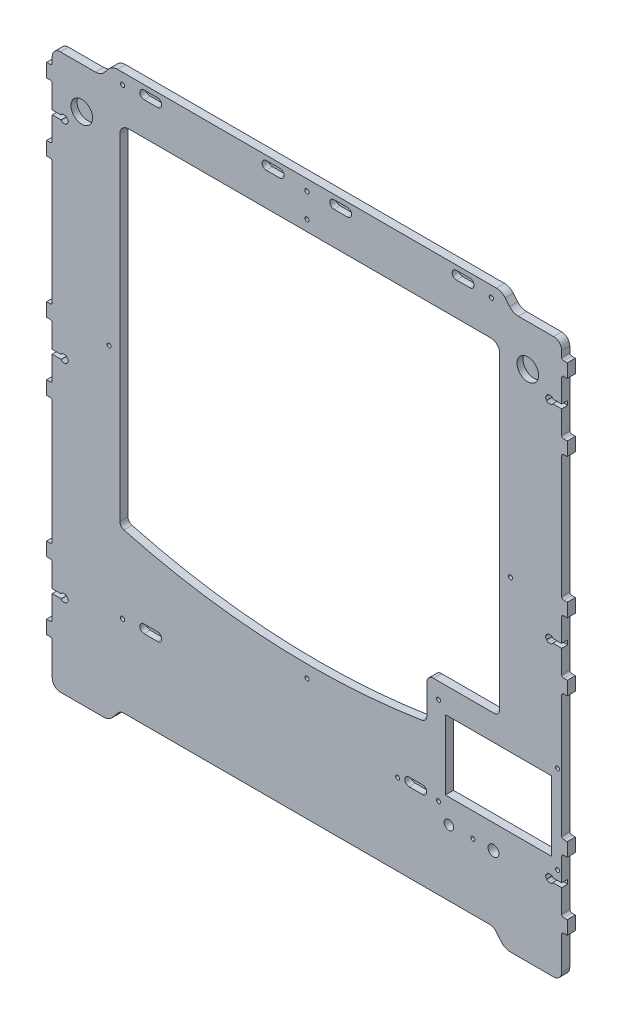
SolidWorks part; units mm, degrees
ref_plane "Alzado" through (0, 0, 0) normal (0, 0, 1) x (1, 0, 0)
ref_plane "Planta" through (0, 0, 0) normal (0, 1, 0) x (1, 0, 0)
ref_plane "Vista lateral" through (0, 0, 0) normal (1, 0, 0) x (0, 0, -1)
sketch "Croquis1" plane through (0, 0, 0) normal (0, 0, 1) x (1, 0, 0)
  line L0 (101.3953, 205.0104) -> (-166.4547, 205.0104)
  line L1 (-34.6047, 239.0104) -> (-34.6047, -170.9896) construction
  line L2 (-172.9547, 198.5104) -> (-172.9547, -49.66)
  line L3 (-222.9547, 187.3104) -> (-34.6047, 187.3104) construction
  line L4 (-128.7797, 34.0104) -> (-128.7797, 187.3104) construction
  line L5 (-222.9547, 205.7604) -> (-222.9547, 168.8604)
  line L6 (107.8953, -30.1228) -> (107.8953, 198.5104)
  line L7 (-222.9547, -87.7396) -> (-222.9547, 2.4604)
  line L8 (153.7453, -87.7396) -> (153.7453, 2.4604)
  line L9 (-227.1047, 167.3104) -> (-224.5047, 167.3104)
  line L10 (103.8762, -34.1419) -> (58.9808, -34.1419)
  line L11 (54.0552, -39.0675) -> (54.0552, -60.8574)
  line L12 (-227.1047, 157.3104) -> (-227.1047, 167.3104)
  line L13 (-224.5047, 157.3104) -> (-227.1047, 157.3104)
  line L14 (-224.5047, -89.2896) -> (-227.1047, -89.2896)
  line L15 (-227.1047, -89.2896) -> (-227.1047, -99.2896)
  line L16 (-34.6047, 34.0104) -> (-222.9547, 34.0104) construction
  line L17 (-227.1047, -99.2896) -> (-224.5047, -99.2896)
  line L21 (-227.1047, -139.2896) -> (-224.5047, -139.2896)
  line L22 (-227.1047, -149.2896) -> (-227.1047, -139.2896)
  line L23 (-224.5047, -149.2896) -> (-227.1047, -149.2896)
  line L25 (-222.9547, -137.7396) -> (-222.9547, -100.8396)
  line L32 (147.7453, -180.9896) -> (115.7453, -180.9896)
  line L36 (100.8221, -170.9896) -> (-170.0314, -170.9896)
  line L37 (-210.4105, 34.0104) -> (-223.8121, 34.0104) construction
  line L38 (-222.9547, 15.5604) -> (-222.9547, 52.4604)
  line L42 (153.7453, 37.4611) -> (153.7453, -87.7396) construction
  line L43 (-227.1047, 14.0104) -> (-224.5047, 14.0104)
  line L44 (-227.1047, 4.0104) -> (-227.1047, 14.0104)
  line L45 (-224.5047, 4.0104) -> (-227.1047, 4.0104)
  line L46 (-224.5047, 64.0104) -> (-227.1047, 64.0104)
  line L47 (-227.1047, 64.0104) -> (-227.1047, 54.0104)
  line L48 (-227.1047, 54.0104) -> (-224.5047, 54.0104)
  line L63 (-34.6047, 34.0104) -> (153.7453, 34.0104) construction
  line L69 (109.234, -177.9533) -> (105.0418, -172.9573)
  line L73 (-222.9547, 155.7604) -> (-222.9547, 65.5604)
  line L74 (-222.9547, 37.4611) -> (-222.9547, -87.7396) construction
  line L75 (-222.9547, -150.8396) -> (-222.9547, -174.9896)
  line L77 (153.7453, -150.8396) -> (153.7453, -174.9896)
  line L81 (157.8953, -99.2896) -> (155.2953, -99.2896)
  line L82 (157.8953, -89.2896) -> (157.8953, -99.2896)
  line L83 (155.2953, -89.2896) -> (157.8953, -89.2896)
  line L84 (155.2953, -149.2896) -> (157.8953, -149.2896)
  line L85 (157.8953, -149.2896) -> (157.8953, -139.2896)
  line L86 (157.8953, -139.2896) -> (155.2953, -139.2896)
  line L87 (153.7453, -137.7396) -> (153.7453, -100.8396)
  line L91 (155.2953, 4.0104) -> (157.8953, 4.0104)
  line L92 (157.8953, 4.0104) -> (157.8953, 14.0104)
  line L93 (157.8953, 14.0104) -> (155.2953, 14.0104)
  line L103 (153.7453, 15.5604) -> (153.7453, 52.4604)
  line L104 (157.8953, 54.0104) -> (155.2953, 54.0104)
  line L105 (157.8953, 64.0104) -> (157.8953, 54.0104)
  line L106 (155.2953, 64.0104) -> (157.8953, 64.0104)
  line L107 (153.7453, 155.7604) -> (153.7453, 65.5604)
  line L108 (155.2953, 157.3104) -> (157.8953, 157.3104)
  line L109 (157.8953, 157.3104) -> (157.8953, 167.3104)
  line L110 (157.8953, 167.3104) -> (155.2953, 167.3104)
  line L115 (153.7453, 205.7604) -> (153.7453, 168.8604)
  line L116 (157.8953, 207.3104) -> (155.2953, 207.3104)
  line L117 (157.8953, 217.3104) -> (157.8953, 207.3104)
  line L118 (155.2953, 217.3104) -> (157.8953, 217.3104)
  line L119 (153.7453, 223.1104) -> (153.7453, 218.8604)
  line L120 (121.7453, 229.1104) -> (147.7453, 229.1104)
  line L121 (112.0224, 235.9741) -> (115.234, 232.1467)
  line L131 (105.511, 239.0104) -> (-174.7203, 239.0104)
  line L132 (-181.2317, 235.9741) -> (-184.4433, 232.1467)
  line L133 (-190.9547, 229.1104) -> (-216.9547, 229.1104)
  line L134 (-222.9547, 223.1104) -> (-222.9547, 218.8604)
  line L135 (-224.5047, 217.3104) -> (-227.1047, 217.3104)
  line L136 (-227.1047, 217.3104) -> (-227.1047, 207.3104)
  line L137 (-227.1047, 207.3104) -> (-224.5047, 207.3104)
  line L142 (-216.9547, -180.9896) -> (-184.9547, -180.9896)
  line L143 (-178.4433, -177.9533) -> (-174.2511, -172.9573)
  line L145 (-222.9547, 110.6604) -> (-34.6047, 110.6604) construction
  arc A0 (-172.9547, -49.66) -> (-169.9851, -53.6034) centre (-168.8516, -49.66) ccw
  arc A1 (107.8953, 198.5104) -> (101.3953, 205.0104) centre (101.3953, 198.5104) ccw
  arc A2 (-222.9547, 168.8604) -> (-224.5047, 167.3104) centre (-224.5047, 168.8604) cw
  arc A3 (-224.5047, 157.3104) -> (-222.9547, 155.7604) centre (-224.5047, 155.7604) cw
  arc A4 (-166.4547, 205.0104) -> (-172.9547, 198.5104) centre (-166.4547, 198.5104) ccw
  arc A5 (103.8762, -34.1419) -> (107.8953, -30.1228) centre (103.8762, -30.1228) ccw
  arc A7 (-224.5047, -89.2896) -> (-222.9547, -87.7396) centre (-224.5047, -87.7396) ccw
  arc A8 (-222.9547, -100.8396) -> (-224.5047, -99.2896) centre (-224.5047, -100.8396) ccw
  arc A9 (-222.9547, -137.7396) -> (-224.5047, -139.2896) centre (-224.5047, -137.7396) cw
  arc A10 (50.2783, -65.2775) -> (-169.9851, -53.6034) centre (-32.4058, 458.4336) cw
  arc A11 (50.2783, -65.2775) -> (54.0552, -60.8574) centre (49.5804, -60.8574) ccw
  arc A12 (58.9808, -34.1419) -> (54.0552, -39.0675) centre (58.9808, -39.0675) ccw
  arc A15 (-224.5047, -149.2896) -> (-222.9547, -150.8396) centre (-224.5047, -150.8396) cw
  arc A18 (-222.9547, -174.9896) -> (-216.9547, -180.9896) centre (-216.9547, -174.9896) ccw
  arc A28 (-222.9547, 15.5604) -> (-224.5047, 14.0104) centre (-224.5047, 15.5604) cw
  arc A29 (-224.5047, 4.0104) -> (-222.9547, 2.4604) centre (-224.5047, 2.4604) cw
  arc A30 (-224.5047, 64.0104) -> (-222.9547, 65.5604) centre (-224.5047, 65.5604) ccw
  arc A31 (-222.9547, 52.4604) -> (-224.5047, 54.0104) centre (-224.5047, 52.4604) ccw
  arc A40 (100.8221, -170.9896) -> (105.0418, -172.9573) centre (100.8221, -176.498) cw
  arc A41 (115.7453, -180.9896) -> (109.234, -177.9533) centre (115.7453, -172.4896) cw
  arc A42 (153.7453, -174.9896) -> (147.7453, -180.9896) centre (147.7453, -174.9896) cw
  arc A45 (153.7453, -100.8396) -> (155.2953, -99.2896) centre (155.2953, -100.8396) cw
  arc A62 (155.2953, -89.2896) -> (153.7453, -87.7396) centre (155.2953, -87.7396) cw
  arc A63 (155.2953, -149.2896) -> (153.7453, -150.8396) centre (155.2953, -150.8396) ccw
  arc A64 (153.7453, -137.7396) -> (155.2953, -139.2896) centre (155.2953, -137.7396) ccw
  arc A68 (155.2953, 4.0104) -> (153.7453, 2.4604) centre (155.2953, 2.4604) ccw
  arc A69 (153.7453, 15.5604) -> (155.2953, 14.0104) centre (155.2953, 15.5604) ccw
  circle A70 centre (101.7453, 231.0104) radius 1.6
  circle A71 centre (-34.6047, 231.0104) radius 1.6
  arc A75 (153.7453, 52.4604) -> (155.2953, 54.0104) centre (155.2953, 52.4604) cw
  arc A76 (155.2953, 64.0104) -> (153.7453, 65.5604) centre (155.2953, 65.5604) cw
  arc A77 (155.2953, 157.3104) -> (153.7453, 155.7604) centre (155.2953, 155.7604) ccw
  arc A78 (153.7453, 168.8604) -> (155.2953, 167.3104) centre (155.2953, 168.8604) ccw
  arc A83 (153.7453, 205.7604) -> (155.2953, 207.3104) centre (155.2953, 205.7604) cw
  arc A84 (155.2953, 217.3104) -> (153.7453, 218.8604) centre (155.2953, 218.8604) cw
  arc A85 (147.7453, 229.1104) -> (153.7453, 223.1104) centre (147.7453, 223.1104) cw
  arc A86 (121.7453, 229.1104) -> (115.234, 232.1467) centre (121.7453, 237.6104) cw
  arc A87 (105.511, 239.0104) -> (112.0224, 235.9741) centre (105.511, 230.5104) cw
  arc A89 (-174.7203, 239.0104) -> (-181.2317, 235.9741) centre (-174.7203, 230.5104) ccw
  arc A90 (-190.9547, 229.1104) -> (-184.4433, 232.1467) centre (-190.9547, 237.6104) ccw
  arc A91 (-216.9547, 229.1104) -> (-222.9547, 223.1104) centre (-216.9547, 223.1104) ccw
  arc A92 (-224.5047, 217.3104) -> (-222.9547, 218.8604) centre (-224.5047, 218.8604) ccw
  arc A93 (-222.9547, 205.7604) -> (-224.5047, 207.3104) centre (-224.5047, 205.7604) ccw
  arc A97 (-184.9547, -180.9896) -> (-178.4433, -177.9533) centre (-184.9547, -172.4896) ccw
  arc A98 (-170.0314, -170.9896) -> (-174.2511, -172.9573) centre (-170.0314, -176.498) ccw
  circle A108 centre (-170.9547, 231.0104) radius 1.6
  circle A133 centre (-170.9547, -110.9896) radius 1.6
  dimension "D1" = 8.5
  dimension "D3" = 8.5
  dimension "D4" = 6
  dimension "D8" = 1.55
  dimension "D11" = 1.55
  dimension "D14" = 50
  dimension "D21" = 6
  dimension "D23" = 40
  dimension "D26" = 8
  dimension "D27" = 32
  dimension "D29" = 3.2
  dimension "D30" = 8.5
  dimension "D7" = 3.2
  dimension "D20" = 13
  dimension "D87" = 1.55
  dimension "D88" = 1.55
  dimension "D22" = 13
  dimension "D2" = 50
  dimension "D5" = 8
  dimension "D6" = 52
  dimension "D9" = 10
  dimension "D10" = 2.6
  dimension "D13" = 50
  dimension "D16" = 34
  dimension "D17" = 11.8
  dimension "D18" = 32
  dimension "D19" = 15.9
  dimension "D28" = 52
  dimension "D32" = 10
  dimension "D33" = 6.5218
  dimension "D34" = 50
  dimension "D85" = 10
  dimension "D86" = 2.6
  dimension "Alto_panel" = 420
  dimension "Ancho_panel" = 385
extrude "Saliente-Extruir1" add sketch "Croquis1" along normal blind 6 contours A98 L36 L117 A86 L108 L105 A69 region at (-219.3798, 210.8852, 0)
sketch "Croquis10" plane through (0, 0, 6) normal (0, 0, 1) x (1, 0, 0)
  line L0 (153.7453, 205.7604) -> (153.7453, 168.8604) construction
  line L2 (101.7453, -110.9896) -> (183.8923, -110.9896) construction
  line L3 (-216.4544, 188.8604) -> (-222.9547, 188.8604)
  line L4 (-209.8753, 187.3104) -> (-223.8121, 187.3104) construction
  line L5 (-214.9445, 190.0604) -> (-213.3945, 190.0604)
  line L6 (-211.8813, 188.8465) -> (-211.8813, 188.6773)
  line L7 (-222.9547, 34.0104) -> (153.7453, 34.0104) construction
  line L8 (-211.8813, 185.9436) -> (-211.8813, 185.7743)
  line L9 (-214.9445, 184.5604) -> (-213.3945, 184.5604)
  line L10 (-222.9547, 188.8604) -> (-222.9547, 185.7604)
  line L11 (-34.6047, 239.0104) -> (-34.6047, -170.9896) construction
  line L12 (105.511, 239.0104) -> (-174.7203, 239.0104) construction
  line L13 (100.8221, -170.9896) -> (-170.0314, -170.9896) construction
  line L14 (-222.9547, 15.5604) -> (-222.9547, 52.4604) construction
  line L15 (-216.4544, 185.7604) -> (-222.9547, 185.7604)
  line L16 (-222.9547, 110.6604) -> (-34.6047, 110.6604) construction
  line L17 (-222.9547, 155.7604) -> (-222.9547, 65.5604) construction
  line L18 (-209.8753, 34.0104) -> (-223.8121, 34.0104) construction
  line L19 (-216.4544, 35.5604) -> (-222.9547, 35.5604)
  line L20 (-222.9547, 32.4604) -> (-222.9547, 35.5604)
  line L21 (-214.9445, 36.7604) -> (-213.3945, 36.7604)
  line L22 (-211.8813, 35.3773) -> (-211.8813, 35.5465)
  line L23 (-211.8813, 32.4743) -> (-211.8813, 32.6436)
  line L24 (-214.9445, 31.2604) -> (-213.3945, 31.2604)
  line L25 (-216.4544, 32.4604) -> (-222.9547, 32.4604)
  line L26 (-209.8753, -119.2896) -> (-223.8121, -119.2896) construction
  line L27 (-216.4544, -117.7396) -> (-222.9547, -117.7396)
  line L28 (-222.9547, -120.8396) -> (-222.9547, -117.7396)
  line L29 (-214.9445, -116.5396) -> (-213.3945, -116.5396)
  line L30 (-211.8813, -117.9227) -> (-211.8813, -117.7535)
  line L31 (-211.8813, -120.8257) -> (-211.8813, -120.6564)
  line L32 (-214.9445, -122.0396) -> (-213.3945, -122.0396)
  line L33 (-216.4544, -120.8396) -> (-222.9547, -120.8396)
  line L34 (140.666, -119.2896) -> (154.6028, -119.2896) construction
  line L35 (147.2451, -120.8396) -> (153.7453, -120.8396)
  line L36 (145.7352, -122.0396) -> (144.1852, -122.0396)
  line L37 (142.672, -120.8257) -> (142.672, -120.6564)
  line L38 (142.672, -117.9227) -> (142.672, -117.7535)
  line L39 (145.7352, -116.5396) -> (144.1852, -116.5396)
  line L40 (153.7453, -120.8396) -> (153.7453, -117.7396)
  line L41 (147.2451, -117.7396) -> (153.7453, -117.7396)
  line L42 (140.666, 34.0104) -> (154.6028, 34.0104) construction
  line L43 (147.2451, 32.4604) -> (153.7453, 32.4604)
  line L44 (145.7352, 31.2604) -> (144.1852, 31.2604)
  line L45 (142.672, 32.4743) -> (142.672, 32.6436)
  line L46 (142.672, 35.3773) -> (142.672, 35.5465)
  line L47 (145.7352, 36.7604) -> (144.1852, 36.7604)
  line L48 (153.7453, 32.4604) -> (153.7453, 35.5604)
  line L49 (147.2451, 35.5604) -> (153.7453, 35.5604)
  line L50 (140.666, 187.3104) -> (154.6028, 187.3104) construction
  line L51 (147.2451, 185.7604) -> (153.7453, 185.7604)
  line L52 (153.7453, 188.8604) -> (153.7453, 185.7604)
  line L53 (145.7352, 184.5604) -> (144.1852, 184.5604)
  line L54 (142.672, 185.9436) -> (142.672, 185.7743)
  line L55 (142.672, 188.8465) -> (142.672, 188.6773)
  line L56 (145.7352, 190.0604) -> (144.1852, 190.0604)
  line L57 (147.2451, 188.8604) -> (153.7453, 188.8604)
  line L58 (-64.6047, 235.6104) -> (-54.6047, 235.6104)
  line L59 (-64.6047, 229.4104) -> (-54.6047, 229.4104)
  line L60 (153.7453, 15.5604) -> (153.7453, 52.4604) construction
  line L61 (-155.1047, 235.6104) -> (-145.1047, 235.6104)
  line L62 (-155.1047, 229.4104) -> (-145.1047, 229.4104)
  line L63 (-54.6047, 229.4104) -> (-145.1047, 229.4104) construction
  line L64 (-4.6047, 229.4104) -> (-14.6047, 229.4104)
  line L65 (-4.6047, 235.6104) -> (-14.6047, 235.6104)
  line L66 (85.8953, 235.6104) -> (75.8953, 235.6104)
  line L67 (85.8953, 229.4104) -> (75.8953, 229.4104)
  line L68 (153.7453, -137.7396) -> (153.7453, -100.8396) construction
  line L69 (150.7453, -110.9896) -> (150.7453, -109.4896) construction
  line L70 (-155.1047, -106.3896) -> (-145.1047, -106.3896)
  line L71 (-155.1047, -112.5896) -> (-145.1047, -112.5896)
  line L72 (150.7453, -45.9896) -> (150.4025, -45.9896) construction
  line L73 (62.7453, -45.9896) -> (62.7453, -110.9896) construction
  line L76 (-54.6047, 229.4104) -> (-59.2707, -112.5578) construction
  line L77 (71.4025, -45.9896) -> (33.4932, -45.9896) construction
  line L78 (-190.9547, 229.1104) -> (-216.9547, 229.1104) construction
  line L79 (-227.1047, 64.0104) -> (-227.1047, 54.0104) construction
  line L80 (-227.1047, 59.0104) -> (157.8953, 59.0104) construction
  line L81 (157.8953, 64.0104) -> (157.8953, 54.0104) construction
  line L82 (-222.9547, 205.7604) -> (-222.9547, 168.8604) construction
  line L83 (-4.6047, -112.5896) -> (-14.6047, -112.5896) [skipped]
  line L84 (-4.6047, -106.3896) -> (-14.6047, -106.3896) [skipped]
  line L85 (-64.6047, -112.5896) -> (-54.6047, -112.5896) [skipped]
  line L86 (-64.6047, -106.3896) -> (-54.6047, -106.3896) [skipped]
  line L87 (75.8953, -106.3896) -> (28.0463, -106.3896) construction
  line L88 (150.7453, -46.4164) -> (150.7453, -27.838) construction
  line L89 (150.7374, -109.4896) -> (150.7453, -110.9896) construction
  line L90 (150.4025, -45.9896) -> (164.7294, -45.9896) construction
  line L91 (67.7453, -52.9896) -> (146.2453, -52.9896)
  line L92 (67.7453, -52.9896) -> (67.7453, -104.4896)
  line L93 (67.7453, -104.4896) -> (146.2453, -104.4896)
  line L94 (146.2453, -52.9896) -> (146.2453, -104.4896)
  line L95 (62.7453, -45.9896) -> (149.2453, -45.9896) construction
  line L96 (75.8953, -112.5896) -> (26.3993, -112.5896) construction
  line L97 (50.8953, -104.4896) -> (50.8953, -114.379) construction
  line L99 (50.8953, -106.3896) -> (40.8953, -106.3896)
  line L100 (50.8953, -112.5896) -> (40.8953, -112.5896)
  line L101 (85.8953, -106.3896) -> (75.8953, -106.3896) [skipped]
  line L102 (85.8953, -112.5896) -> (75.8953, -112.5896) [skipped]
  circle A0 centre (128.7453, 198.6104) radius 8
  circle A1 centre (-201.1047, 198.6104) radius 8
  arc A2 (-214.9445, 36.7604) -> (-216.4544, 35.5604) centre (-214.9445, 35.2104) ccw
  circle A3 centre (-170.9547, -110.9896) radius 1.6 construction
  arc A4 (-211.8813, 32.4743) -> (-213.3945, 31.2604) centre (-213.3945, 32.8104) cw
  arc A5 (-214.9445, 31.2604) -> (-216.4544, 32.4604) centre (-214.9445, 32.8104) cw
  arc A6 (-211.8813, 35.5465) -> (-213.3945, 36.7604) centre (-213.3945, 35.2104) ccw
  arc A7 (-211.8813, 35.3773) -> (-211.8813, 32.6436) centre (-212.6118, 34.0104) cw
  arc A8 (-211.8813, 185.9436) -> (-211.8813, 188.6773) centre (-212.6118, 187.3104) ccw
  arc A9 (-214.9445, -116.5396) -> (-216.4544, -117.7396) centre (-214.9445, -118.0896) ccw
  arc A10 (-211.8813, -120.8257) -> (-213.3945, -122.0396) centre (-213.3945, -120.4896) cw
  arc A11 (-214.9445, -122.0396) -> (-216.4544, -120.8396) centre (-214.9445, -120.4896) cw
  arc A12 (-211.8813, -117.7535) -> (-213.3945, -116.5396) centre (-213.3945, -118.0896) ccw
  arc A13 (-211.8813, -117.9227) -> (-211.8813, -120.6564) centre (-212.6118, -119.2896) cw
  arc A14 (142.672, -117.9227) -> (142.672, -120.6564) centre (143.4025, -119.2896) ccw
  arc A15 (142.672, -117.7535) -> (144.1852, -116.5396) centre (144.1852, -118.0896) cw
  arc A16 (145.7352, -122.0396) -> (147.2451, -120.8396) centre (145.7352, -120.4896) ccw
  arc A17 (142.672, -120.8257) -> (144.1852, -122.0396) centre (144.1852, -120.4896) ccw
  arc A18 (145.7352, -116.5396) -> (147.2451, -117.7396) centre (145.7352, -118.0896) cw
  arc A19 (142.672, 35.3773) -> (142.672, 32.6436) centre (143.4025, 34.0104) ccw
  arc A20 (142.672, 35.5465) -> (144.1852, 36.7604) centre (144.1852, 35.2104) cw
  arc A21 (145.7352, 31.2604) -> (147.2451, 32.4604) centre (145.7352, 32.8104) ccw
  arc A22 (142.672, 32.4743) -> (144.1852, 31.2604) centre (144.1852, 32.8104) ccw
  arc A23 (145.7352, 36.7604) -> (147.2451, 35.5604) centre (145.7352, 35.2104) cw
  arc A24 (145.7352, 184.5604) -> (147.2451, 185.7604) centre (145.7352, 186.1104) ccw
  arc A25 (142.672, 188.8465) -> (144.1852, 190.0604) centre (144.1852, 188.5104) cw
  arc A26 (145.7352, 190.0604) -> (147.2451, 188.8604) centre (145.7352, 188.5104) cw
  arc A27 (142.672, 185.7743) -> (144.1852, 184.5604) centre (144.1852, 186.1104) ccw
  arc A28 (142.672, 185.9436) -> (142.672, 188.6773) centre (143.4025, 187.3104) cw
  arc A29 (-54.6047, 229.4104) -> (-54.6047, 235.6104) centre (-54.6047, 232.5104) ccw
  arc A30 (-64.6047, 235.6104) -> (-64.6047, 229.4104) centre (-64.6047, 232.5104) ccw
  arc A31 (-145.1047, 229.4104) -> (-145.1047, 235.6104) centre (-145.1047, 232.5104) ccw
  arc A32 (-155.1047, 235.6104) -> (-155.1047, 229.4104) centre (-155.1047, 232.5104) ccw
  arc A33 (-14.6047, 229.4104) -> (-14.6047, 235.6104) centre (-14.6047, 232.5104) cw
  arc A34 (-4.6047, 235.6104) -> (-4.6047, 229.4104) centre (-4.6047, 232.5104) cw
  arc A35 (75.8953, 229.4104) -> (75.8953, 235.6104) centre (75.8953, 232.5104) cw
  arc A36 (85.8953, 235.6104) -> (85.8953, 229.4104) centre (85.8953, 232.5104) cw
  circle A37 centre (150.7453, -110.9896) radius 1.5
  circle A38 centre (150.7453, -45.9896) radius 1.5
  arc A39 (-145.1047, -112.5896) -> (-145.1047, -106.3896) centre (-145.1047, -109.4896) ccw
  arc A40 (-155.1047, -106.3896) -> (-155.1047, -112.5896) centre (-155.1047, -109.4896) ccw
  circle A41 centre (62.7453, -45.9896) radius 1.5
  circle A42 centre (62.7453, -110.9896) radius 1.5
  arc A45 (40.8953, -112.5896) -> (40.8953, -106.3896) centre (40.8953, -109.4896) cw
  arc A46 (50.8953, -106.3896) -> (50.8953, -112.5896) centre (50.8953, -109.4896) cw
  arc A63 (-211.8813, 185.7743) -> (-213.3945, 184.5604) centre (-213.3945, 186.1104) cw
  arc A65 (-214.9445, 190.0604) -> (-216.4544, 188.8604) centre (-214.9445, 188.5104) ccw
  arc A66 (-211.8813, 188.8465) -> (-213.3945, 190.0604) centre (-213.3945, 188.5104) ccw
  arc A67 (-214.9445, 184.5604) -> (-216.4544, 185.7604) centre (-214.9445, 186.1104) cw
  arc A68 (-14.6047, -112.5896) -> (-14.6047, -106.3896) centre (-14.6047, -109.4896) cw [skipped]
  arc A69 (-4.6047, -106.3896) -> (-4.6047, -112.5896) centre (-4.6047, -109.4896) cw [skipped]
  arc A70 (-54.6047, -112.5896) -> (-54.6047, -106.3896) centre (-54.6047, -109.4896) ccw [skipped]
  arc A71 (-64.6047, -106.3896) -> (-64.6047, -112.5896) centre (-64.6047, -109.4896) ccw [skipped]
  arc A72 (85.8953, -106.3896) -> (85.8953, -112.5896) centre (85.8953, -109.4896) cw [skipped]
  arc A73 (75.8953, -112.5896) -> (75.8953, -106.3896) centre (75.8953, -109.4896) cw [skipped]
  dimension "D4" = 6.2
  dimension "D5" = 10
  dimension "D12" = 6.5002
  dimension "D3" = 16
  dimension "D13" = 1.55
  dimension "D15" = 1.55
  dimension "D17" = 1.5498
  dimension "D9" = 40.4
  dimension "D21" = 21.85
  dimension "D26" = 3
  dimension "D27" = 65
  dimension "D28" = 88
  dimension "D29" = 65
  dimension "D6" = 20
  dimension "D7" = 6.5
  dimension "D10" = 15.85
  dimension "D14" = 1.55
  dimension "D16" = 0.1692
  dimension "D18" = 41.8
  dimension "D19" = 1.55
  dimension "D20" = 1.2
  dimension "D22" = 25
  dimension "D23" = 2.7365
  dimension "D24" = 1.3669
  dimension "D30" = 78.5
  dimension "D31" = 51.5
  dimension "D32" = 40.4
  dimension "D33" = 5
  dimension "D34" = 7
  dimension "D8" = 2
  dimension "D11" = 2
  dimension "Distancia_vert_entre_horizontales_ensambles" = 342
extrude "Cortar-Extruir4" cut sketch "Croquis10" against normal blind 4.5
sketch "Croquis12" plane through (0, 0, 6) normal (0, 0, 1) x (1, 0, 0)
  line L0 (146.2453, -52.9896) -> (67.7453, -52.9896) construction
  line L1 (67.7453, -52.9896) -> (67.7453, -104.4896) construction
  line L2 (146.2453, -104.4896) -> (146.2453, -52.9896) construction
  line L3 (67.7453, -104.4896) -> (146.2453, -104.4896) construction
  line L4 (146.2453, -52.9896) -> (67.7453, -52.9896)
  line L5 (67.7453, -52.9896) -> (67.7453, -104.4896)
  line L6 (146.2453, -104.4896) -> (146.2453, -52.9896)
  line L7 (67.7453, -104.4896) -> (146.2453, -104.4896)
  line L8 (62.7453, -110.9896) -> (62.7453, -146.2874) construction
  line L9 (62.7453, -122.3396) -> (113.5642, -122.3396) construction
  line L10 (62.7453, -110.9896) -> (118.9149, -110.9896) construction
  circle A0 centre (150.7453, -110.9896) radius 1.5 construction
  circle A1 centre (150.7453, -45.9896) radius 1.5 construction
  circle A2 centre (62.7453, -45.9896) radius 1.5 construction
  circle A3 centre (62.7453, -110.9896) radius 1.5 construction
  circle A4 centre (150.7453, -110.9896) radius 1.5
  circle A5 centre (150.7453, -45.9896) radius 1.5
  circle A6 centre (62.7453, -45.9896) radius 1.5
  circle A7 centre (62.7453, -110.9896) radius 1.5
  circle A8 centre (70.3453, -122.3396) radius 3.5
  circle A9 centre (88.0953, -122.3396) radius 1.5
  circle A10 centre (103.3453, -122.3396) radius 4
  dimension "D2" = 7.6
  dimension "D3" = 17.75
  dimension "D4" = 33
  dimension "D1" = 11.35
extrude "Cortar-Extruir5" cut sketch "Croquis12" against normal blind 6
sketch "Croquis13" plane through (0, 0, 6) normal (0, 0, 1) x (1, 0, 0)
  line L1 (96.4703, -107.5672) -> (108.9592, -107.5672)
  line L2 (96.4703, -107.5672) -> (96.4703, -114.7394)
  line L3 (96.4703, -114.7394) -> (108.9592, -114.7394)
  line L4 (108.9592, -107.5672) -> (108.9592, -114.7394)
extrude "Saliente-Extruir2" add sketch "Croquis13" against normal blind 6
sketch "Croquis14" plane through (0, 0, 6) normal (0, 0, 1) x (1, 0, 0)
  line L0 (62.7453, -110.9896) -> (2.0273, -110.9896) construction
  line L1 (40.8953, -106.3896) -> (40.8953, -124.7124) construction
  line L2 (32.7453, -105.4686) -> (32.7453, -121.3905) construction
  circle A0 centre (62.7453, -110.9896) radius 1.5 construction
  circle A1 centre (62.7453, -110.9896) radius 1.5
  circle A2 centre (32.3863, -110.9896) radius 1.5
  dimension "D1" = 8.15
extrude "Cortar-Extruir6" cut sketch "Croquis14" against normal blind 6
sketch "Croquis15" plane through (0, 0, 0) normal (0, 0, -1) x (-1, 0, 0)
  line L0 (34.6047, 231.0104) -> (34.6047, -170.9896) construction
  line L1 (-100.8221, -170.9896) -> (170.0314, -170.9896) construction
  line L2 (-157.8953, 59.0104) -> (237.5674, 59.0104) construction
  line L3 (-157.8953, 64.0104) -> (-157.8953, 54.0104) construction
  line L4 (-101.3953, 205.0104) -> (166.4547, 205.0104) construction
  line L5 (-107.8953, -30.1228) -> (-107.8953, 198.5104) construction
  line L6 (172.9547, 198.5104) -> (172.9547, -49.66) construction
  circle A0 centre (34.6047, 213.0104) radius 1.5
  circle A1 centre (-115.8953, 59.0104) radius 1.5
  circle A2 centre (180.9547, 59.0104) radius 1.5
  circle A3 centre (34.6047, -80.9896) radius 1.5
  dimension "D1" = 8
  dimension "D2" = 8
  dimension "D3" = 8
  dimension "D4" = 140
extrude "Cortar-Extruir7" cut sketch "Croquis15" against normal blind 6
equation "\"Ancho_panel\"= 385'Ancho del panel"
equation "\"Alto_panel\"= 420'Alto del panel izquierdo"
equation "\"Altura_base_taladros\"= 70'Alto taladros de la base eje Z"
equation "\"Altura_superior_taladros\"= 8mm'Distancia taladros a top"
equation "\"Distancia_vert_entre_horizontales_ensambles\"= \"Alto_panel\" - \"Altura_base_taladros\" - \"Altura_superior_taladros\"'Distancia vertical entre horizontales de ensambles"
equation "\"Latrales_separacion_barras_a_escalon_bajo\"= 12.5'Separación entre las barras y el escalón inferior de la parte superior"
equation "\"Espacio_tensor_correa_motor\"= 8.5mm'Espacio para mover el motor en vertical y tensar la correa"
